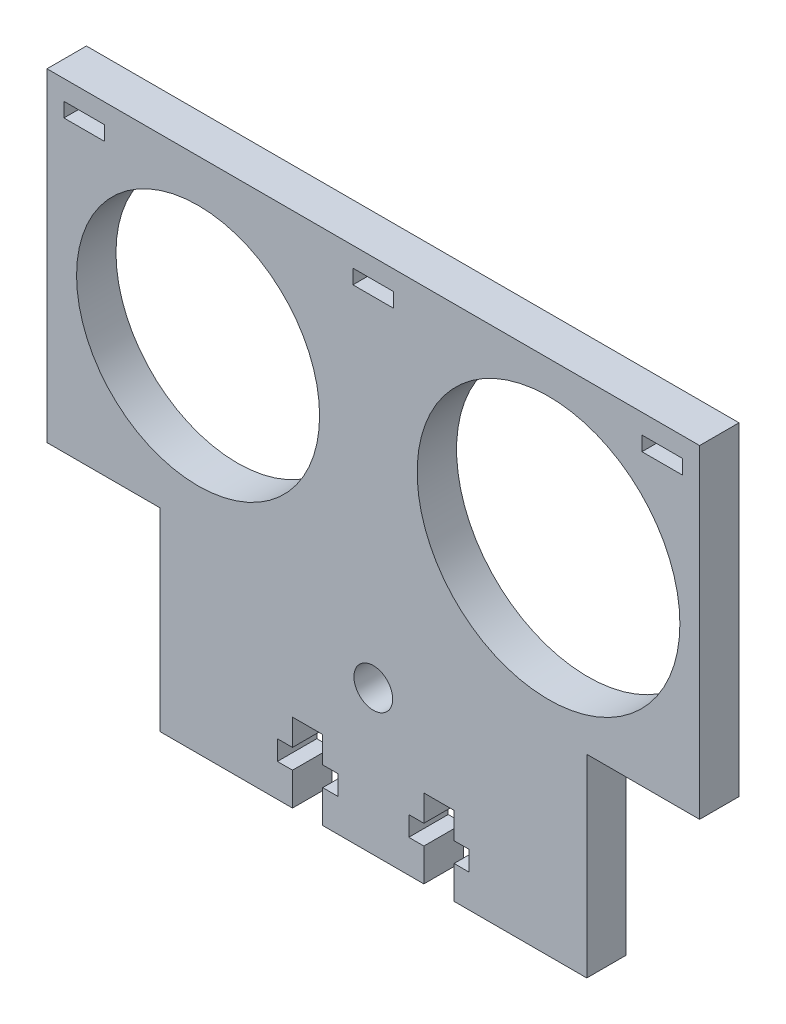
SolidWorks part; units mm, degrees
material "ABS"
ref_plane "Front Plane" through (0, 0, 0) normal (0, 0, 1) x (1, 0, 0)
ref_plane "Top Plane" through (0, 0, 0) normal (0, 1, 0) x (1, 0, 0)
ref_plane "Right Plane" through (0, 0, 0) normal (1, 0, 0) x (0, 0, -1)
sketch "Sketch1" plane through (0, 0, 0) normal (0, 0, 1) x (1, 0, 0)
  line L0 (0, 0) -> (-26.6757, 31.7908) construction
  line L1 (0, 0) -> (0, 56.7908) construction
  line L2 (-32.5, 7.5) -> (-32.5, -22)
  line L3 (-32.5, -22) -> (32.5, -22)
  line L4 (32.5, -22) -> (32.5, 7.5)
  line L5 (0, 0) -> (0, -22) construction
  line L6 (0, 0) -> (26.6757, 31.7908) construction
  line L10 (-32.5, 7.5) -> (-49.6757, 7.5)
  line L11 (-49.6757, 7.5) -> (-49.6757, 56.7908)
  line L12 (-49.6757, 56.7908) -> (49.6757, 56.7908)
  line L13 (49.6757, 56.7908) -> (49.6757, 7.5)
  line L14 (49.6757, 7.5) -> (32.5, 7.5)
  circle A0 centre (0, 0) radius 2.95
  circle A1 centre (26.6757, 31.7908) radius 20
  circle A2 centre (-26.6757, 31.7908) radius 18.5
  dimension "D1" = 5.9
  dimension "D9" = 37
  dimension "D11" = 40
  dimension "D2" = 41.5
  dimension "D4" = 40
  dimension "D5" = 22
  dimension "D6" = 65
  dimension "D3" = 23
  dimension "D7" = 25
  dimension "D8" = 29.5
  dimension "D10" = 40
extrude "Boss-Extrude1" add sketch "Sketch1" along normal blind 6
sketch "Sketch3" plane through (0, 0, 6) normal (0, 0, 1) x (1, 0, 0)
  line L0 (-32.5, -22) -> (32.5, -22) construction
  line L1 (-12.3, -22) -> (-7.7, -22)
  line L2 (-12.3, -22) -> (-12.3, -17)
  line L3 (-12.3, -10) -> (-7.7, -10)
  line L4 (-7.7, -22) -> (-7.7, -17)
  line L5 (0, 0) -> (0, -22) construction
  line L6 (-7.7, -14) -> (-5.4, -14)
  line L7 (-14.6, -14) -> (-12.3, -14)
  line L8 (-14.6, -14) -> (-14.6, -17)
  line L9 (-14.6, -17) -> (-12.3, -17)
  line L10 (-5.4, -14) -> (-5.4, -17)
  line L11 (-12.3, -14) -> (-12.3, -10)
  line L12 (-7.7, -17) -> (-5.4, -17)
  line L13 (-7.7, -14) -> (-7.7, -10)
  line L14 (7.7, -14) -> (7.7, -10)
  line L15 (7.7, -17) -> (5.4, -17)
  line L16 (12.3, -14) -> (12.3, -10)
  line L17 (5.4, -14) -> (5.4, -17)
  line L18 (14.6, -17) -> (12.3, -17)
  line L19 (14.6, -14) -> (14.6, -17)
  line L20 (14.6, -14) -> (12.3, -14)
  line L21 (7.7, -14) -> (5.4, -14)
  line L22 (7.7, -22) -> (7.7, -17)
  line L23 (12.3, -10) -> (7.7, -10)
  line L24 (12.3, -22) -> (12.3, -17)
  line L25 (12.3, -22) -> (7.7, -22)
  point P6 (-10, -10)
  point P18 (-13.45, -17)
  dimension "D1" = 4.6
  dimension "D2" = 10
  dimension "D3" = 12
  dimension "D4" = 9.2
  dimension "D5" = 3
  dimension "D6" = 5
extrude "Cut-Extrude2" cut sketch "Sketch3" against normal through all
sketch "Sketch4" plane through (0, 0, 6) normal (0, 0, 1) x (1, 0, 0)
  line L1 (3.1, 53.7908) -> (-3.1, 53.7908)
  line L2 (3.1, 53.7908) -> (3.1, 51.5908)
  line L3 (3.1, 51.5908) -> (-3.1, 51.5908)
  line L4 (-3.1, 53.7908) -> (-3.1, 51.5908)
  line L5 (47.1, 53.7908) -> (40.9, 53.7908)
  line L6 (47.1, 53.7908) -> (47.1, 51.5908)
  line L7 (47.1, 51.5908) -> (40.9, 51.5908)
  line L8 (40.9, 53.7908) -> (40.9, 51.5908)
  line L9 (-40.9, 53.7908) -> (-47.1, 53.7908)
  line L10 (-40.9, 53.7908) -> (-40.9, 51.5908)
  line L11 (-40.9, 51.5908) -> (-47.1, 51.5908)
  line L12 (-47.1, 53.7908) -> (-47.1, 51.5908)
extrude "Cut-Extrude3" cut sketch "Sketch4" against normal through all
equation "\"smallPulleyTeeth\"= 30"
equation "\"largePulleyTeeth\"= 30"
equation "\"eighthThick\"= 3.0mm"
equation "\"sixteenthThick\"= 1.7mm"
equation "\"quarterThick\"=6.0mm"
equation "\"OD\"= 145mm"
equation "\"puckAngle\"= 60.5deg"
equation "\"puckDiam\"= 76.5mm"
equation "\"axlePress\"= 5.9mm"
equation "\"D1@Sketch1\"=\"axlePress\""
equation "\"D1@Boss-Extrude1\"=\"quarterThick\""
equation "\"press\"= 0.2mm"
equation "\"wheelClear\"= 0.3mm"
equation "\"10-32clear\"= 4.8mm"
equation "\"D1@Sketch3\"=\"10-32clear\"-\"press\""
equation "\"6-32clear\"= 3.3mm"
equation "\"8-32clear\"= 4.0mm"
equation "\"wheelHeight\"= 22mm"
equation "\"D5@Sketch1\"=\"wheelHeight\""
equation "\"4-40clear\"= 3.0mm"
equation "\"wheelWell\"= 65mm"
equation "\"D6@Sketch1\"=\"wheelWell\""
equation "\"D8@Sketch1\"=\"eighthThick\"*10-0.5"
